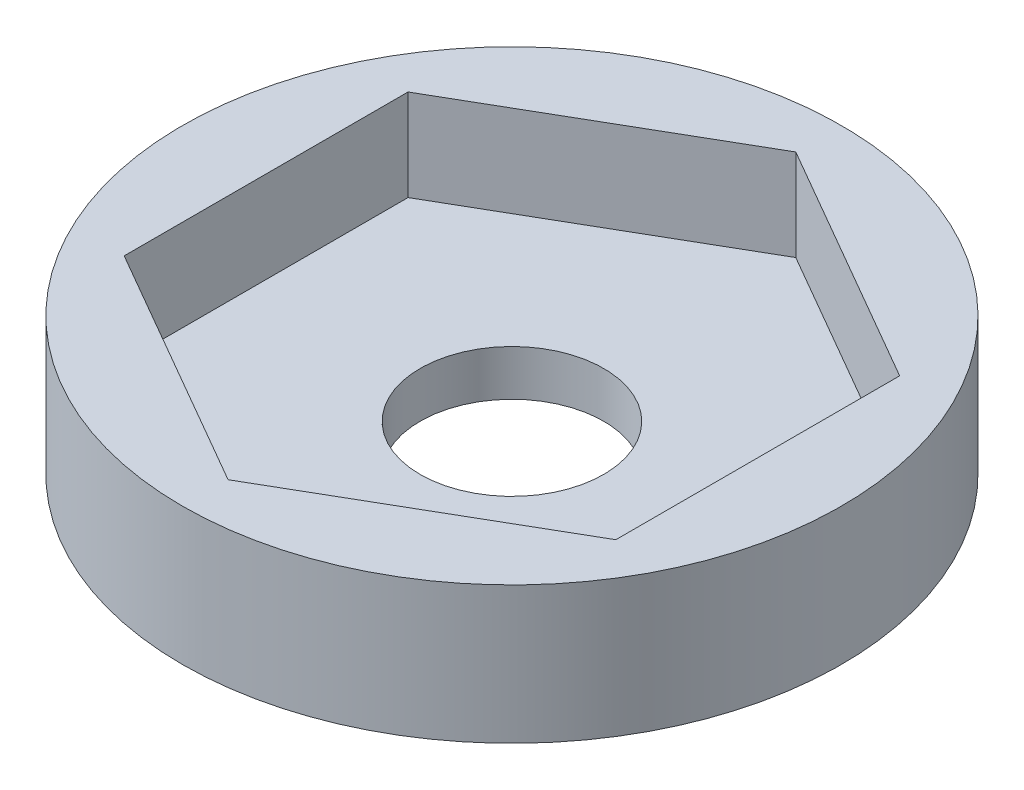
SolidWorks part; units mm, degrees
ref_plane "Front Plane" through (0, 0, 0) normal (0, 0, 1) x (1, 0, 0)
ref_plane "Top Plane" through (0, 0, 0) normal (0, 1, 0) x (1, 0, 0)
ref_plane "Right Plane" through (0, 0, 0) normal (1, 0, 0) x (0, 0, -1)
sketch "Sketch1" plane through (0, 0, 0) normal (0, 1, 0) x (1, 0, 0)
  line L0 (8.5344, -4.9273) -> (9.9092, -5.7211) construction
  line L1 (8.5344, 4.9273) -> (0, 9.8547)
  line L2 (0, 9.8547) -> (-8.5344, 4.9273)
  line L3 (-8.5344, 4.9273) -> (-8.5344, -4.9273)
  line L4 (-8.5344, -4.9273) -> (0, -9.8547)
  line L5 (0, -9.8547) -> (8.5344, -4.9273)
  line L6 (8.5344, -4.9273) -> (8.5344, 4.9273)
  circle A0 centre (0, 0) radius 8.5344 construction
  circle A1 centre (0, 0) radius 11.4422
  dimension "D1" = 17.0688
  dimension "D2" = 1.5875
extrude "Boss-Extrude1" add sketch "Sketch1" along normal blind 3.175
sketch "Sketch2" plane through (0, 0, 0) normal (0, 1, 0) x (1, 0, 0)
  circle A0 centre (0, 0) radius 11.4422
  circle A1 centre (0, 0) radius 3.1877
  circle A2 centre (0, 0) radius 11.4422 construction
  dimension "D1" = 6.3754
extrude "Boss-Extrude2" add sketch "Sketch2" against normal blind 1.5875
sketch "Sketch3" plane through (0, -1.5875, 0) normal (0, -1, 0) x (-1, 0, 0)
  circle A0 centre (0, 0) radius 11.4422
  circle A1 centre (0, 0) radius 11.4422 construction
  circle A2 centre (0, 0) radius 2.794
  dimension "D1" = 5.588
extrude "Boss-Extrude3" [suppressed] add sketch "Sketch3" along normal offset from surface (0.127 mm away) 3.175 from surface
sketch "Sketch4" plane through (0, 0, 0) normal (1, 0, 0) x (0, 0, -1)
  line L0 (11.4422, -1.5875) -> (11.4422, 0)
  line L1 (11.4422, -1.5875) -> (11.4422, 3.175) construction
  line L2 (11.4422, -1.5875) -> (5.569, -1.5875)
  line L3 (-11.4422, -1.5875) -> (11.4422, -1.5875) construction
  line L4 (5.569, -1.5875) -> (5.569, 0.9525)
  line L5 (5.569, 0.9525) -> (11.1346, -0.2483)
  line L6 (11.4422, -1.5875) -> (11.4422, 3.175) construction
  line L7 (4.9273, 0) -> (9.8547, 0) construction
  line L8 (3.1877, -1.5875) -> (3.1877, 0) construction
  line L9 (0, 0) -> (0, -1.5875) construction
  arc A0 (11.4422, 0) -> (11.1346, -0.2483) centre (11.1882, 0) cw
  dimension "D3" = 0.254
  dimension "D1" = 2.54
  dimension "D2" = 2.3813
revolve "Cut-Revolve1" [suppressed] cut sketch "Sketch4" angle 360 about L9
fillet "Fillet1" [suppressed] radius 2.54
